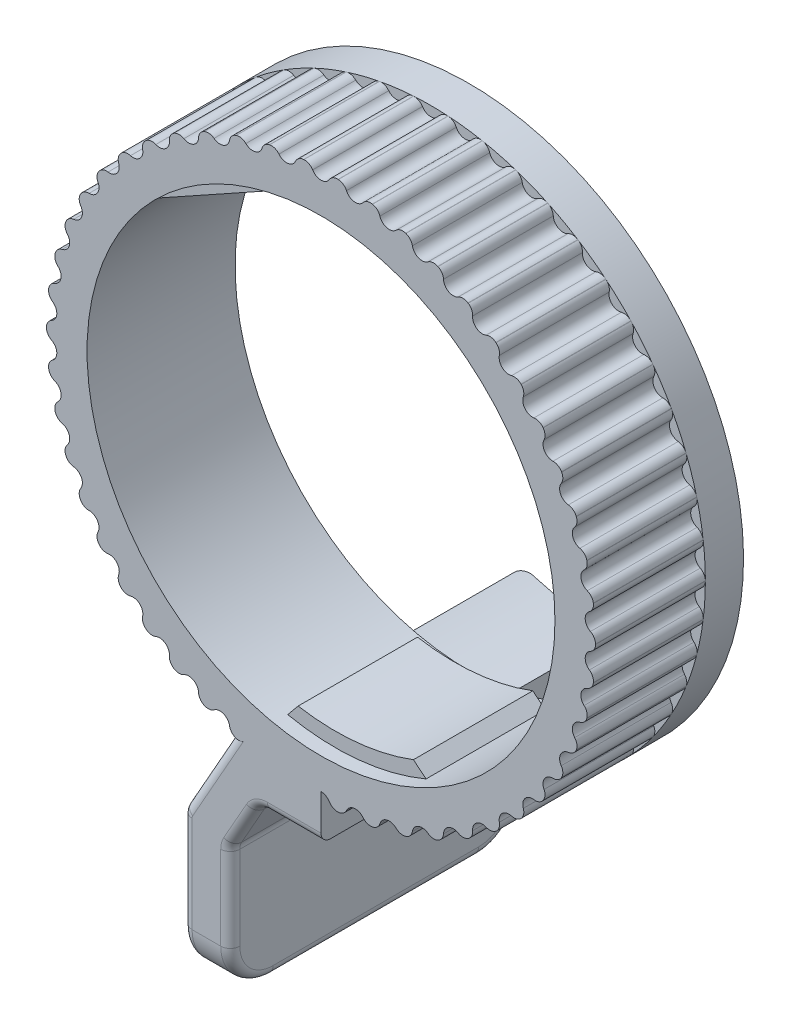
SolidWorks part; units mm, degrees
material "A286 Iron Base Superalloy"
ref_plane "Plane1" through (0, 0, 0) normal (0, 0, 1) x (1, 0, 0)
ref_plane "Plane2" through (0, 0, 0) normal (0, 1, 0) x (1, 0, 0)
ref_plane "Plane3" through (0, 0, 0) normal (1, 0, 0) x (0, 0, -1)
sketch "Sketch1" plane through (0, 0, 0) normal (0, 0, 1) x (1, 0, 0)
  circle A0 centre (0, 0) radius 12.446
  circle A1 centre (0, 0) radius 14.605
  dimension "D1" = 24.892
  dimension "D2" = 29.21
extrude "Base-Extrude" add sketch "Sketch1" along normal mid plane 7.874
sketch "Sketch5" plane through (0, 0, 0) normal (0, 0, 1) x (1, 0, 0)
  line L0 (-2.032, 12.279) -> (-9.3578, 8.2058)
  line L1 (2.032, 12.279) -> (9.3578, 8.2058)
  circle A0 centre (0, 0) radius 12.446 construction
  arc A1 (9.3578, 8.2058) -> (2.032, 12.279) centre (0, 0) ccw
  arc A2 (-2.032, 12.279) -> (-9.3578, 8.2058) centre (0, 0) ccw
  dimension "D1" = 4.064
  dimension "D2" = 8.382
extrude "Boss-Extrude3" add sketch "Sketch5" along normal mid plane 6.35
sketch "Sketch9" plane through (0, 0, 0) normal (0, 0, 1) x (1, 0, 0)
  line L0 (-1.979, -11.5152) -> (-2.5311, -12.1859)
  line L1 (4.1553, -10.9201) -> (4.826, -11.4723)
  arc A0 (-2.5311, -12.1859) -> (4.826, -11.4723) centre (0, 0) ccw
  circle A1 centre (0, 0) radius 11.684
  arc A2 (-1.979, -11.5152) -> (4.1553, -10.9201) centre (0, 0) ccw
  circle A3 centre (0, 0) radius 12.446 construction
  dimension "D2" = 2.5311
  dimension "D3" = 4.826
  dimension "D1" = 0.762
extrude "Boss-Extrude6" add sketch "Sketch9" along normal mid plane 6.35
sketch "Sketch2" plane through (0, 0, 3.937) normal (0, 0, 1) x (1, 0, 0)
  line L0 (0, 0) -> (0, 14.605) construction
  arc A0 (-0.4446, 14.334) -> (0.4446, 14.334) centre (0, 14.605) ccw
  circle A1 centre (0, 0) radius 14.605 construction
  arc A2 (0.91, 14.5766) -> (-0.91, 14.5766) centre (0, 0) ccw
  arc A3 (-0.91, 14.5766) -> (-0.4446, 14.334) centre (-0.8784, 14.0696) cw
  arc A4 (0.91, 14.5766) -> (0.4446, 14.334) centre (0.8784, 14.0696) ccw
  dimension "D1" = 1.0414
  dimension "D2" = 0.508
extrude "Cut-Extrude1" cut sketch "Sketch2" against normal blind 5.842
pattern_circular "CirPattern1" count 50 every 7.2 about axis through (0, 0, 3.937) along (0, 0, -1) of "Cut-Extrude1"
sketch "Sketch6" plane through (0, 0, -3.937) normal (0, 0, -1) x (-1, 0, 0)
  line L0 (0, 0) -> (0, -12.446) construction
  line L1 (0, -12.446) -> (0, -16.51)
  line L2 (0, -16.51) -> (3.302, -16.51)
  line L3 (3.302, -16.51) -> (4.826, -19.2095)
  line L4 (4.826, -19.2095) -> (4.826, -26.162)
  line L5 (4.826, -26.162) -> (7.366, -26.162)
  line L6 (7.366, -26.162) -> (7.366, -18.542)
  line L7 (7.366, -18.542) -> (3.6206, -11.9077)
  arc A0 (0, -12.446) -> (3.6206, -11.9077) centre (0, 0) ccw
  circle A1 centre (0, 0) radius 12.446 construction
  dimension "D1" = 4.064
  dimension "D2" = 2.54
  dimension "D3" = 3.302
  dimension "D4" = 4.826
  dimension "D5" = 9.652
  dimension "D6" = 7.62
  dimension "D7" = 2.54
extrude "Boss-Extrude4" add sketch "Sketch6" against normal through all
sketch "Sketch7" plane through (0, 0, -3.937) normal (0, 0, -1) x (-1, 0, 0)
  line L7 (0, -14.605) -> (0, -16.51)
  line L8 (0, -16.51) -> (3.302, -16.51)
  line L9 (3.302, -16.51) -> (4.826, -19.2095)
  line L10 (4.826, -19.2095) -> (4.826, -26.162)
  line L11 (4.826, -26.162) -> (7.366, -26.162)
  line L12 (7.366, -26.162) -> (7.366, -18.542)
  line L13 (7.366, -18.542) -> (4.704, -13.8267)
  line L14 (0, -14.605) -> (0, -16.51)
  line L15 (0, -16.51) -> (3.302, -16.51)
  line L16 (3.302, -16.51) -> (4.826, -19.2095)
  line L17 (4.826, -19.2095) -> (4.826, -26.162)
  line L18 (4.826, -26.162) -> (7.366, -26.162)
  line L19 (7.366, -26.162) -> (7.366, -18.542)
  line L20 (7.366, -18.542) -> (4.704, -13.8267)
  arc A0 (0, -14.605) -> (4.704, -13.8267) centre (0, 0) ccw
  arc A1 (4.704, -13.8267) -> (0, -14.605) centre (0, 0) ccw
  arc A2 (4.704, -13.8267) -> (0, -14.605) centre (0, 0) ccw construction
  dimension "D1" = 0
extrude "Boss-Extrude5" add sketch "Sketch7" along normal blind 7.62
fillet "Fillet1" radius 2.286 2 edges at (-6.096, -26.162, -11.557) (-6.096, -26.162, 3.937)
fillet "Fillet2" radius 0.762 3 edges at (-3.302, -16.51, -3.81) (-4.826, -19.2095, -3.81) (-7.366, -18.542, -3.81)
fillet "Fillet5" radius 0.508 22 edges at (-1.4286, -16.51, 3.937) (-3.2413, -16.6139, 3.937) (-4.1241, -17.9662, 3.937) (-4.801, -19.216, 3.937) (-4.826, -21.6429, 3.937) (-4.826, -25.4924, 3.2674) (-4.826, -26.162, -3.81) (-4.826, -25.4924, -10.8874) (-4.826, -21.6429, -11.557) (-4.801, -19.216, -11.557) (-4.1241, -17.9662, -11.557) (-3.2413, -16.6139, -11.557) (-1.4286, -16.51, -11.557) (-5.9858, -16.0972, -11.557) (-7.341, -18.5486, -11.557) (-7.366, -21.3091, -11.557) (-7.366, -25.4924, -10.8874) (-7.366, -26.162, -3.81) (-7.366, -25.4924, 3.2674) (-7.366, -21.3091, 3.937) (-7.341, -18.5486, 3.937) (-5.9771, -16.0819, 3.937)
